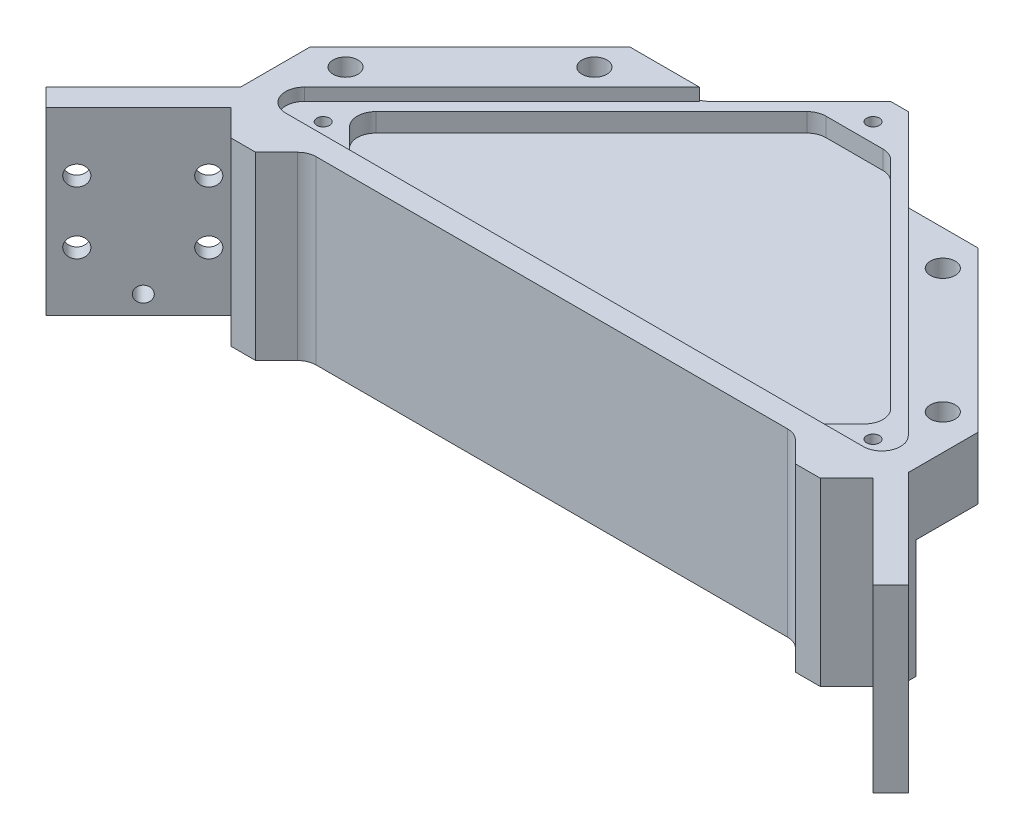
SolidWorks part; units mm, degrees
material "7075-O (SS)"
ref_plane "前视基准面" through (0, 0, 0) normal (0, 0, 1) x (1, 0, 0)
ref_plane "上视基准面" through (0, 0, 0) normal (0, 1, 0) x (1, 0, 0)
ref_plane "右视基准面" through (0, 0, 0) normal (1, 0, 0) x (0, 0, -1)
sketch "草图1" plane through (0, 0, 0) normal (0, 1, 0) x (1, 0, 0)
  line L0 (0, 38.6704) -> (-54.4472, -15.7768) construction
  line L1 (0, 0) -> (0, 38.6704) construction
  line L5 (-54.4472, -15.7768) -> (54.4472, -15.7768) construction
  line L6 (54.4472, -15.7768) -> (0, 38.6704) construction
  line L7 (-53.6569, -14.9865) -> (-69.2965, -30.6261)
  line L8 (-69.2965, -30.6261) -> (-66.468, -33.4545)
  line L9 (-66.468, -33.4545) -> (-51.6188, -18.6053)
  line L10 (-51.6188, -18.6053) -> (-47.3762, -22.8479)
  line L11 (-47.3762, -22.8479) -> (-43.3762, -22.8479)
  line L12 (-43.3762, -22.8479) -> (-39.1335, -18.6053)
  line L13 (-39.1335, -18.6053) -> (0.638, -18.6053)
  line L14 (-5.8284, 30.0135) -> (-43.4871, -7.6451)
  line L15 (-5.8284, 30.0135) -> (5.8284, 30.0135)
  line L16 (43.4871, -7.6451) -> (5.8284, 30.0135)
  line L17 (-37.3553, -13.7768) -> (37.3553, -13.7768)
  line L18 (43.4871, -7.6451) -> (37.3553, -13.7768)
  line L19 (1.4142, 37.2562) -> (-53.033, -17.1911) construction
  line L20 (-43.4871, -7.6451) -> (-37.3553, -13.7768)
  line L21 (-28, 21.88) -> (-53.6569, -3.7768)
  line L22 (0, 6.2232) -> (-44.9675, 6.2232) construction
  line L23 (-28, 16.2232) -> (-48, -3.7768) construction
  line L24 (-38, 6.2232) -> (-44.9994, 13.2225) construction
  line L25 (-30.8284, 19.0516) -> (-50.8284, -0.9484) construction
  line L26 (-28, 21.88) -> (-16.7904, 21.88)
  line L27 (-53.6569, -3.7768) -> (-53.6569, -14.9865)
  line L28 (-16.7904, 21.88) -> (0, 38.6704)
  line L29 (28, 21.88) -> (16.7904, 21.88)
  line L30 (16.7904, 21.88) -> (0, 38.6704)
  line L31 (28, 21.88) -> (53.6569, -3.7768)
  line L32 (53.6569, -3.7768) -> (53.6569, -14.9865)
  line L33 (39.1335, -18.6053) -> (0.638, -18.6053)
  line L34 (43.3762, -22.8479) -> (39.1335, -18.6053)
  line L35 (47.3762, -22.8479) -> (43.3762, -22.8479)
  line L36 (51.6188, -18.6053) -> (47.3762, -22.8479)
  line L37 (66.468, -33.4545) -> (51.6188, -18.6053)
  line L38 (53.6569, -14.9865) -> (69.2965, -30.6261)
  line L39 (69.2965, -30.6261) -> (66.468, -33.4545)
  line L40 (-28, 16.2232) -> (-34.4664, 22.6895) construction
  circle A3 centre (0, 33.0135) radius 1
  circle A4 centre (-44.1942, -11.1806) radius 1
  circle A5 centre (44.1942, -11.1806) radius 1
  circle A6 centre (-48, -3.7768) radius 2
  circle A7 centre (-28, 16.2232) radius 2
  circle A8 centre (28, 16.2232) radius 2
  circle A9 centre (48, -3.7768) radius 2
  point P19 (53.033, -17.1911)
  point P20 (-1.4142, 37.2562)
  point P21 (-54.4472, -13.7768)
  point P22 (54.4472, -13.7768)
  point P38 (-21.2511, 17.4193)
  dimension "D1" = 77
  dimension "D3" = 4
  dimension "D4" = 2
  dimension "D5" = 2
  dimension "D7" = 21
  dimension "D12" = 62.5
  dimension "D13" = 62.5
  dimension "D16" = 3
  dimension "D19" = 10
  dimension "D20" = 4
  dimension "D21" = 48
  dimension "D22" = 30
  dimension "D23" = 4
  dimension "D2" = 90
  dimension "D6" = 2
  dimension "D8" = 4
  dimension "D9" = 6
  dimension "D10" = 4
  dimension "D11" = 6
  dimension "D14" = 2
  dimension "D15" = 3
  dimension "D17" = 2
  dimension "D18" = 20
  dimension "D24" = 4
  dimension "D25" = 21
extrude "凸台-拉伸1" add sketch "草图1" against normal blind 29 contours L14 L20 L17 L18 L16 L15 | L39 L38 L32 L31 L29 L30 L28 L26 L21 L27 L7 L8 L9 L10 L11 L12 L13 L33 L34 L35 L36 L37 A8 A7 A6 A5 A4 A3 L20 L14 L15 L16 L18 L17 A9 region at (-52.0945, 0, 9.3817) region at (0, 0, -2.8045)
extrude "切除-拉伸1" cut sketch "草图1<3>" against normal blind 5 contours L14 L20 L17 L18 L16 L15 region at (0, 0, -2.8045)
sketch "草图1<3>" plane through (0, 0, 0) normal (0, 1, 0) x (1, 0, 0) same geometry as "草图1"
sketch "草图3" plane through (0, 0, 0) normal (0, 1, 0) x (1, 0, 0)
  line L0 (-74.1272, -13.7768) -> (70.6324, -13.7768)
  line L1 (70.6324, -13.7768) -> (4.5985, 56.318)
  line L2 (4.5985, 56.318) -> (-74.1272, -13.7768)
extrude "切除-拉伸2" cut sketch "草图3" against normal blind 19 from offset 10 offset against normal yes
sketch "草图4" plane through (0, 0, 0) normal (0, 1, 0) x (1, 0, 0)
  line L0 (-2.1213, 36.5491) -> (-48.5355, -9.8652)
  line L1 (-46.4142, -14.9865) -> (46.4142, -14.9865)
  line L2 (48.5355, -9.8652) -> (0, 38.6704)
  line L3 (-2.1213, 36.5491) -> (0, 38.6704)
  arc A0 (48.5355, -9.8652) -> (46.4142, -14.9865) centre (46.4142, -11.9865) cw
  arc A1 (-46.4142, -14.9865) -> (-48.5355, -9.8652) centre (-46.4142, -11.9865) cw
  point P8 (53.6569, -14.9865)
  point P11 (-53.6569, -14.9865)
  point P14 (0, 38.6704)
  dimension "D1" = 3
extrude "切除-拉伸3" cut sketch "草图4" against normal blind 2
sketch "草图11" plane through (-16.5068, 0, -16.5068) normal (0.7071, 0, 0.7071) x (0.7071, 0, -0.7071)
  line L4 (-67.1559, -19.5) -> (-52.1559, -19.5) construction
  line L5 (-67.1559, -19.5) -> (-67.1559, -9.5) construction
  line L6 (-67.1559, -9.5) -> (-52.1559, -9.5) construction
  line L7 (-52.1559, -19.5) -> (-52.1559, -9.5) construction
  line L8 (-67.1559, -19.5) -> (-52.1559, -9.5) construction
  line L9 (-67.1559, -9.5) -> (-52.1559, -19.5) construction
  line L11 (-49.6559, -29) -> (-49.6559, 0) construction
  line L12 (-70.6559, -29) -> (-49.6559, -29) construction
  circle A0 centre (-52.1559, -9.5) radius 1.6
  circle A1 centre (-52.1559, -19.5) radius 1.6
  circle A2 centre (-67.1559, -19.5) radius 1.6
  circle A3 centre (-67.1559, -9.5) radius 1.6
  point P3 (-59.6559, -14.5)
  point P6 (-59.6559, -14.5)
  dimension "D5" = 3.2
  dimension "D1" = 15
  dimension "D2" = 10
  dimension "D3" = 2.5
  dimension "D4" = 9.5
extrude "切除-拉伸4" cut sketch "草图11" against normal through all
sketch "草图13" plane through (-19.3352, 0, -19.3352) normal (-0.7071, 0, -0.7071) x (-0.7071, 0, 0.7071)
  line L0 (59.597, 0) -> (59.597, -29) construction
  line L1 (48.5382, 0) -> (70.6559, 0) construction
  line L2 (48.5382, -29) -> (70.6559, -29) construction
  circle A0 centre (59.597, -26) radius 1.25
  dimension "D1" = 3
  dimension "D2" = 2.5
extrude "切除-拉伸5" cut sketch "草图13" against normal blind 2
cosmetic thread "孔螺蚊线4" parameters "D2"=3
cosmetic thread "孔螺蚊线5" parameters "D2"=3
hole_wizard "M2.5 螺纹孔6" positions "3D草图3" profile "草图8" tap size "M2.5" standard "GB" end condition through all
sketch3d "3D草图3"
  line L0 (0, -10, -33.0135) -> (0, -2, -33.0135) construction
  line L1 (-44.1942, -10, 11.1806) -> (-44.1942, -2, 11.1806) construction
  line L2 (44.1942, -10, 11.1806) -> (44.1942, -2, 11.1806) construction
  point P0 (0, -2, -33.0135)
  point P4 (-44.1942, -2, 11.1806)
  point P8 (44.1942, -2, 11.1806)
sketch "草图8" plane through (0, -2, -33.0135) normal (1, 0, 0) x (0, 0, 1)
  line L0 (0, 0) -> (0, 27)
  line L1 (0, 27) -> (1.025, 27)
  line L2 (1.025, 27) -> (1.025, 0)
  line L5 (1.025, 0) -> (0, 0)
  line L11 (0, -6.35) -> (0, 107.95) construction
  dimension "通孔螺纹孔钻头直径" = 2.05
  dimension "通孔螺纹孔钻头深度" = 27
cosmetic thread "孔螺蚊线1" parameters "D2"=2.5
cosmetic thread "孔螺蚊线2" parameters "D2"=2.5
cosmetic thread "孔螺蚊线3" parameters "D2"=2.5
hole_wizard "M3 螺纹孔1" positions "3D草图6" profile "草图14" tap size "M3" standard "GB" end condition through all
sketch3d "3D草图6"
  line L0 (-60.0624, -26, 24.2205) -> (-61.4767, -26, 22.8063) construction
  point P0 (-61.4767, -26, 22.8063)
sketch "草图14" plane through (-61.4767, -26, 22.8063) normal (0, 1, 0) x (-0.7071, 0, 0.7071)
  line L0 (0, 0) -> (0, 100)
  line L1 (0, 100) -> (1.25, 100)
  line L2 (1.25, 100) -> (1.25, 0.275)
  line L3 (1.25, 0.275) -> (1.525, 0)
  line L5 (1.525, 0) -> (0, 0)
  line L6 (-1.25, 0.275) -> (-1.525, 0) construction
  line L11 (0, -6.35) -> (0, 107.95) construction
  dimension "通孔螺纹孔钻头直径" = 2.5
  dimension "通孔螺纹孔钻头深度" = 100
  dimension "近端锥形沉头孔直径" = 3.05
  dimension "近端锥形沉头孔角度" = 90
ref_plane "基准面1" through (0, 0, 0) normal (-1, 0, 0) x (0, 0, 1)
mirror "镜向2" about plane through (0, 0, 0) normal (-1, 0, 0) of "M3 螺纹孔1", "切除-拉伸5", "切除-拉伸4"
chamfer "倒角1" distance 2 angle 45 1 edges at (0, -6, -38.6704)
fillet "圆角1" radius 3 10 edges at (43.4871, -3.5, 7.6451) (37.3553, -3.5, 13.7768) (-37.3553, -3.5, 13.7768) (-43.4871, -3.5, 7.6451) (5.8284, -3.5, -30.0135) (-5.8284, -3.5, -30.0135) (-39.1335, -14.5, 18.6053) (39.1335, -14.5, 18.6053) (16.7904, -6, -21.88) (-16.7904, -6, -21.88)
chamfer "倒角2" distance 1.65 angle 45 8 edges at (-67.953, -9.5, 29.2826) (-67.953, -19.5, 29.2826) (-57.3464, -19.5, 18.676) (-57.3464, -9.5, 18.676) (57.3464, -19.5, 18.676) (67.953, -19.5, 29.2826) (67.953, -9.5, 29.2826) (57.3464, -9.5, 18.676)
